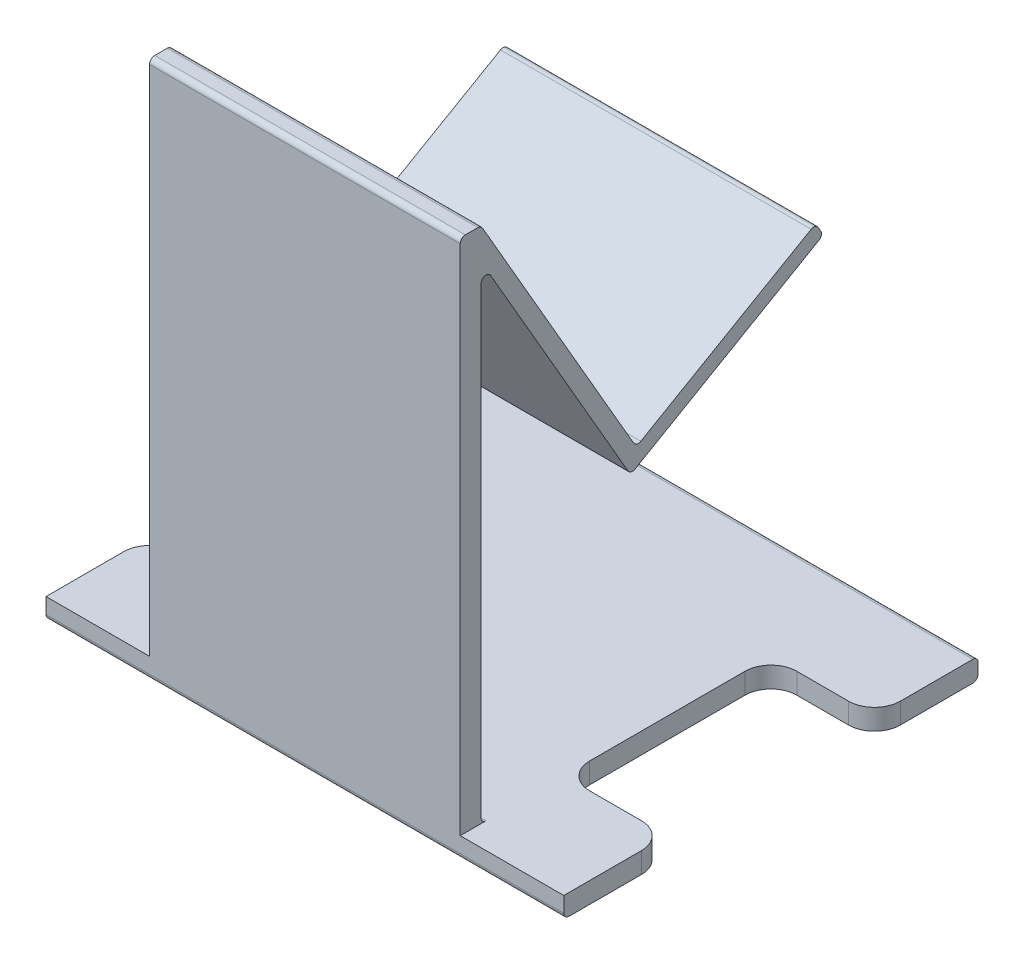
SolidWorks part; units mm, degrees
ref_plane "前视基准面" through (0, 0, 0) normal (0, 0, 1) x (1, 0, 0)
ref_plane "上视基准面" through (0, 0, 0) normal (0, 1, 0) x (1, 0, 0)
ref_plane "右视基准面" through (0, 0, 0) normal (1, 0, 0) x (0, 0, -1)
other "Configuration Table"
sketch "草图1" plane through (0, 0, 0) normal (1, 0, 0) x (0, 0, -1)
  line L0 (4.2887, 103.5) -> (33.5, 52.9045)
  line L1 (1, 0) -> (79, 0)
  line L2 (0, 1) -> (0, 4)
  line L3 (5, 4) -> (79, 4)
  line L4 (80, 1) -> (80, 3)
  line L6 (0, 4) -> (0, 103)
  line L7 (1, 104) -> (3.4226, 104)
  line L8 (4, 5) -> (4, 94.2679)
  line L9 (34.866, 52.5385) -> (67.775, 71.5385)
  line L10 (69.141, 71.1725) -> (69.641, 70.3064)
  line L11 (69.275, 68.9404) -> (33.7679, 48.4404)
  line L12 (32.4019, 48.8064) -> (5.866, 94.7679)
  line L13 (20, 4) -> (20, 0)
  line L14 (60, 4) -> (60, 0)
  line L15 (5, 4) -> (0, 4)
  arc A0 (79, 0) -> (80, 1) centre (79, 1) ccw
  arc A1 (79, 4) -> (80, 3) centre (79, 3) cw
  arc A2 (1, 0) -> (0, 1) centre (1, 1) cw
  arc A3 (5, 4) -> (4, 5) centre (5, 5) cw
  arc A4 (69.641, 70.3064) -> (69.275, 68.9404) centre (68.775, 69.8064) cw
  arc A5 (67.775, 71.5385) -> (69.141, 71.1725) centre (68.275, 70.6725) cw
  arc A6 (33.7679, 48.4404) -> (32.4019, 48.8064) centre (33.2679, 49.3064) cw
  arc A7 (33.5, 52.9045) -> (34.866, 52.5385) centre (34.366, 53.4045) ccw
  arc A8 (5.866, 94.7679) -> (4, 94.2679) centre (5, 94.2679) ccw
  arc A9 (3.4226, 104) -> (4.2887, 103.5) centre (3.4226, 103) cw
  arc A10 (0, 103) -> (1, 104) centre (1, 103) cw
  point P16 (80, 0)
  point P19 (80, 4)
  point P22 (0, 0)
  point P25 (4, 4)
  point P28 (70.141, 69.4404)
  point P31 (68.641, 72.0385)
  point P36 (34, 52.0385)
  point P39 (4, 98)
  point P42 (4, 104)
  point P45 (0, 104)
  dimension "D12" = 1
  dimension "D1" = 80
  dimension "D2" = 4
  dimension "D3" = 100
  dimension "D4" = 4
  dimension "D5" = 3
  dimension "D6" = 3
  dimension "D7" = 30
  dimension "D8" = 40
  dimension "D9" = 60
  dimension "D10" = 94
  dimension "D11" = 4
  dimension "D13" = 20
  dimension "D14" = 20
extrude "凸台-拉伸1" add sketch "草图1" along normal mid plane 60 contours A10 L6 L2 A2 L1 L13 L3 A3 L8 A8 L12 A6 L11 A4 L10 A5 L9 A7 L0 A9 L7 | L14 L3 L13 L1 | A1 L3 L14 L1 A0 L4 | A2 L1 L13 L3 L15 L2 region at (0, 77.5926, -17.8383) region at (0, 2.0048, -10.0263) region at (0, 2, -40) region at (0, 2, -69.9473)
extrude "凸台-拉伸2" add sketch "草图1<4>" along normal mid plane 100 contours A2 L1 L13 L3 L15 L2 | A1 L3 L14 L1 A0 L4 region at (0, 2.0048, -10.0263) region at (0, 2, -69.9473)
sketch "草图1<4>" plane through (0, 0, 0) normal (1, 0, 0) x (0, 0, -1) same geometry as "草图1"
fillet "圆角1" radius 5 8 edges at (-50, 2, -20) (-30, 2, -20) (-50, 2, -60) (-30, 2, -60) (50, 2, -20) (50, 2, -60) (30, 2, -60) (30, 2, -20)
